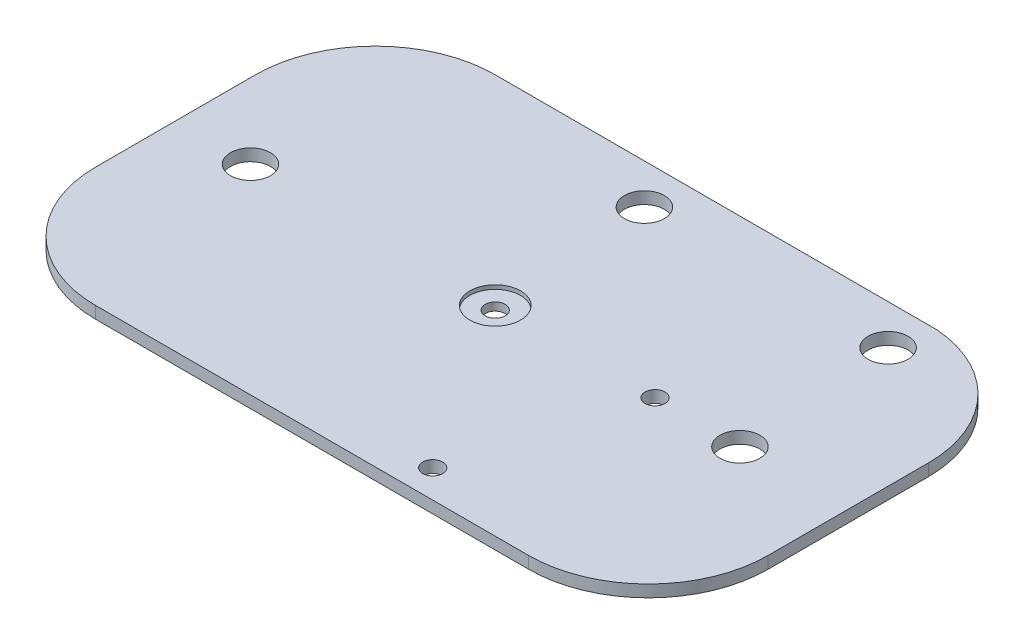
SolidWorks part; units mm, degrees
ref_plane "前视基准面" through (0, 0, 0) normal (0, 0, 1) x (1, 0, 0)
ref_plane "上视基准面" through (0, 0, 0) normal (0, 1, 0) x (1, 0, 0)
ref_plane "右视基准面" through (0, 0, 0) normal (1, 0, 0) x (0, 0, -1)
other "Configuration Table"
sketch "草图1" plane through (0, 0, 0) normal (0, 1, 0) x (1, 0, 0)
  line L0 (50, 0) -> (50, 85.1816) construction
  line L1 (0, 0) -> (100, 0)
  line L2 (0, 0) -> (0, -100)
  line L3 (0, -100) -> (100, -100)
  line L4 (100, 0) -> (100, -100)
  line L5 (9.5, 75.0478) -> (9.5, 17.1128) construction
  line L6 (90.5, 75.0478) -> (90.5, 17.1128) construction
  line L7 (-7.6482, 80) -> (134.4168, 80) construction
  line L8 (0, 0) -> (9.5, 12.5)
  line L9 (100, 0) -> (90.5, 12.5)
  line L10 (90.5, 12.5) -> (90.5, 212.5)
  line L11 (90.5, 212.5) -> (9.5, 212.5)
  line L12 (9.5, 212.5) -> (9.5, 12.5)
  line L13 (90.5, 12.5) -> (90.5, 0)
  line L14 (9.5, 12.5) -> (9.5, 0)
  dimension "D1" = 100
  dimension "D2" = 100
  dimension "D3" = 81
  dimension "D4" = 80
  dimension "D5" = 200
extrude "凸台-拉伸1" add sketch "草图1" along normal blind 50 and the other way blind 50 contours L12 L14 L1 L13 L10 L11 region at (50, 0, -106.25)
ref_plane "基准面1" through (0, 0, 0) normal (0, -1, 0) x (-1, 0, 0)
sketch "草图2" plane through (0, 0, 0) normal (0, -1, 0) x (-1, 0, 0)
  line L0 (-130.3132, 0) -> (40.2206, 0) construction
  line L1 (-150, 0) -> (-150, -100)
  line L2 (-150, -100) -> (50, -100)
  line L3 (50, -100) -> (50, 0)
  line L4 (50, 0) -> (-150, 0)
  line L5 (-50, 212.5) -> (-50, 195.989) construction
  line L6 (-90.5, 212.5) -> (-9.5, 212.5) construction
  point P10 (-50, 212.5)
  dimension "D1" = 200
  dimension "D2" = 100
extrude "凸台-拉伸2" add sketch "草图2" against normal blind 40
ref_plane "基准面2" through (0, 0, 100) normal (0, 0, 1) x (1, 0, 0)
sketch "草图3" plane through (0, 0, 100) normal (0, 0, 1) x (1, 0, 0)
  line L0 (-50, 37) -> (150, 37)
  line L1 (-50, 40) -> (-50, 0) construction
  line L2 (150, 40) -> (150, 0) construction
  line L3 (150, 37) -> (150, 3)
  line L4 (150, 3) -> (-50, 3)
  line L5 (-50, 3) -> (-50, 37)
  line L6 (150, 0) -> (-50, 0) construction
  line L7 (150, 40) -> (-50, 40) construction
  dimension "D1" = 3
  dimension "D2" = 3
extrude "切除-拉伸1" cut sketch "草图3" against normal blind 100
ref_plane "基准面3" through (34.5, 0, 0) normal (-1, 0, 0) x (0, 0, 1)
ref_plane "基准面4" through (0, 50, 0) normal (0, 1, 0) x (1, 0, 0)
sketch "草图6" plane through (0, 50, 0) normal (0, 1, 0) x (1, 0, 0)
  line L0 (12.5, 212.5) -> (12.5, 5)
  line L1 (90.5, 212.5) -> (9.5, 212.5) construction
  line L2 (12.5, 5) -> (87.5, 5)
  line L3 (87.5, 5) -> (87.5, 212.5)
  line L4 (9.5, 212.5) -> (9.5, 0) construction
  line L5 (90.5, 212.5) -> (90.5, 0) construction
  line L7 (9.5, 0) -> (90.5, 0) construction
  dimension "D1" = 3
  dimension "D2" = 3
  dimension "D3" = 5
extrude "切除-拉伸2" cut sketch "草图6" against normal through all
ref_plane "基准面5" through (0, 40, 0) normal (0, 1, 0) x (1, 0, 0)
sketch "草图8" plane through (0, 40, 0) normal (0, 1, 0) x (1, 0, 0)
  line L0 (-50, -50) -> (102.2011, -50) construction
  line L1 (-50, -100) -> (-50, 0) construction
  line L2 (50, 0) -> (50, -100) construction
  line L3 (9.5, 0) -> (90.5, 0) construction
  line L4 (-22, -100) -> (22, -100) construction
  circle A0 centre (70, -50) radius 2.5
  circle A1 centre (30, -50) radius 2.5
  dimension "D1" = 5
  dimension "D2" = 5
  dimension "D3" = 40
extrude "切除-拉伸4" cut sketch "草图8" against normal through all
ref_plane "基准面6" through (90.5, 0, 0) normal (1, 0, 0) x (0, 0, -1)
sketch "草图10" plane through (90.5, 0, 0) normal (1, 0, 0) x (0, 0, -1)
  line L0 (39.5916, 0) -> (155.7144, 0) construction
  line L2 (0, 37) -> (0, 3) construction
  circle A0 centre (80, 0) radius 5
  circle A1 centre (180, 0) radius 5
  dimension "D3" = 10
  dimension "D4" = 10
  dimension "D1" = 80
  dimension "D2" = 180
extrude "切除-拉伸5" cut sketch "草图10" against normal through all
sketch "草图11" plane through (9.5, 0, 0) normal (-1, 0, 0) x (0, 0, 1)
  line L2 (-30.9056, 83.4152) -> (-74.0944, 50)
  line L3 (44.55, 50) -> (-44.55, 50) construction
  line L4 (-74.0944, 50) -> (0, 50)
  line L5 (0, 40) -> (0, 50) construction
  line L6 (0, 50) -> (0, 40)
  line L8 (-30.9056, 83.4152) -> (83.321, 40)
  line L9 (100, 40) -> (0, 40) construction
  line L10 (83.321, 40) -> (0, 40)
extrude "凸台-拉伸5" add sketch "草图11" against normal blind 10
sketch "草图13" plane through (90.5, 0, 0) normal (1, 0, 0) x (0, 0, -1)
  line L0 (0, 36.2107) -> (0, 62.8442) construction
  line L1 (44.55, 50) -> (-44.55, 50) construction
  line L2 (74.1158, 50) -> (0, 50)
  line L3 (74.1158, 50) -> (74.1158, 53)
  line L4 (74.1158, 53) -> (0, 53)
  line L5 (0, 50) -> (0, 53)
  dimension "D1" = 3
extrude "凸台-拉伸7" add sketch "草图13" against normal blind 81
ref_plane "基准面7" through (12.5, 0, 0) normal (1, 0, 0) x (0, 0, -1)
sketch "草图14" plane through (12.5, 0, 0) normal (1, 0, 0) x (0, 0, -1)
  line L0 (5, -46.5508) -> (5, 34.4221) construction
  line L2 (5, -50) -> (212.5, -50)
  line L3 (212.5, -50) -> (212.5, 50)
  line L4 (44.55, 50) -> (-44.55, 50) construction
  line L5 (212.5, -50) -> (212.5, 50) construction
  line L6 (212.5, 50) -> (5, 50)
  line L7 (5, 50) -> (5, -50)
extrude "凸台-拉伸8" add sketch "草图14" along normal blind 7
sketch "草图15" plane through (90.5, 0, 0) normal (1, 0, 0) x (0, 0, -1)
  line L0 (30.9056, 83.4152) -> (-82.9022, 40)
  line L1 (55, 40) -> (-55, 40) construction
  line L2 (-82.9022, 40) -> (0, 40)
  line L3 (0, 37) -> (0, 40) construction
  line L4 (0, 40) -> (0, 53)
  line L5 (0, 53) -> (70.217, 53)
  line L6 (70.217, 53) -> (30.9056, 83.4152)
extrude "凸台-拉伸9" add sketch "草图15" against normal blind 10
ref_plane "基准面8" through (0, 37, 0) normal (0, -1, 0) x (-1, 0, 0)
ref_plane "基准面9" through (0, 3, 0) normal (0, 1, 0) x (1, 0, 0)
sketch "草图17" plane through (0, 37, 0) normal (0, -1, 0) x (-1, 0, 0)
  circle A0 centre (-30, -50) radius 6.35
  dimension "D1" = 12.7
extrude "切除-拉伸6" cut sketch "草图17" against normal blind 1
sketch "草图18" plane through (0, 3, 0) normal (0, 1, 0) x (1, 0, 0)
  circle A0 centre (30, -50) radius 6.35
  dimension "D1" = 12.7
extrude "切除-拉伸7" cut sketch "草图18" against normal blind 1
sketch "草图20" plane through (0, 0, 0) normal (0, -1, 0) x (1, 0, 0)
  line L0 (7.57, 50) -> (34.6356, 50) construction
  line L1 (30, 52.5) -> (30, 68.4286) construction
  circle A1 centre (-31.25, 50) radius 5
  circle A2 centre (91.25, 50) radius 5
  dimension "D2" = 10
  dimension "D4" = 10
  dimension "D1" = 61.25
  dimension "D3" = 61.25
extrude "切除-拉伸8" cut sketch "草图20" against normal blind 3
cosmetic thread "装饰螺纹线1" parameters "D2"=11
cosmetic thread "装饰螺纹线2" parameters "D2"=11
sketch "草图21" plane through (0, 3, 0) normal (0, 1, 0) x (1, 0, 0)
  line L0 (118.3346, -100) -> (118.3346, 0)
  line L1 (-22, -100) -> (22, -100) construction
  line L2 (90.5, 0) -> (150, 0) construction
  line L3 (118.3346, 0) -> (150, 0)
  line L4 (150, 0) -> (150, -100)
  line L5 (150, 0) -> (150, -100) construction
  line L6 (150, -100) -> (118.3346, -100)
extrude "切除-拉伸9" cut sketch "草图21" along normal through all both and the other way through all
sketch "草图22" plane through (0, 0, 0) normal (0, -1, 0) x (1, 0, 0)
  line L0 (-38.0419, 14.9384) -> (110.8032, 14.9384) construction
  circle A0 centre (-28.835, 14.9384) radius 5
  circle A1 centre (99.9437, 14.9384) radius 5
  circle A2 centre (47.3586, 88.9028) radius 5
  dimension "D1" = 10
  dimension "D2" = 10
  dimension "D3" = 10
extrude "凸台-拉伸10" add sketch "草图22" against normal up to surface (37 mm away) up to face at (70, 37, 52.5)
fillet "圆角1" radius 30 10 edges at (14.5, 83.4152, -30.9056) (85.5, 83.4152, -30.9056) (118.3346, 38.5, 0) (118.3346, 1.5, 0) (118.3346, 38.5, 100) (118.3346, 1.5, 100) (-50, 38.5, 100) (-50, 38.5, 0) (-50, 1.5, 0) (-50, 1.5, 100)
fillet "圆角2" radius 30 2 edges at (89, -50, -212.5) (89, 50, -212.5)
sketch "草图23" plane through (19.5, 0, 0) normal (1, 0, 0) x (0, 0, -1)
  line L0 (-82.9022, 40) -> (15.1729, 77.4135)
  line L1 (55, 40) -> (-55, 40) construction
  line L2 (15.1729, 77.4135) -> (-82.9022, 40) construction
  line L3 (15.1729, 77.4135) -> (30.2606, 83.1692)
  line L4 (30.2606, 83.1692) -> (82.9117, 53.4848)
  line L5 (82.9117, 53.4848) -> (216.9824, 51.4008)
  line L6 (216.9824, 51.4008) -> (216.9824, -53.0307)
  line L7 (216.9824, -53.0307) -> (0, -55.3463)
  line L8 (0, -55.3463) -> (0, 40)
  line L9 (0, 40) -> (-82.9022, 40)
  arc A0 (44.2235, 73.1112) -> (15.1729, 77.4135) centre (25.8656, 49.3838) ccw construction
extrude "切除-拉伸10" cut sketch "草图23" against normal through all both and the other way through all
ref_plane "基准面10" through (0, 0, 0) normal (0, -1, 0) x (-1, 0, 0)
sketch "草图24" plane through (0, 0, 0) normal (0, -1, 0) x (1, 0, 0)
  line L0 (-36.25, 50) -> (-26.25, 50) construction
  line L1 (-50, 66.8294) -> (-50, 70)
  line L2 (-50, 70) -> (-50, 30) construction
  line L3 (1.65, 100) -> (-1.65, 100) construction
  line L4 (-20, 100) -> (88.3346, 100)
  line L5 (118.3346, 70) -> (118.3346, 30)
  line L6 (88.3346, 0) -> (-20, 0)
  line L7 (-50, 0) -> (-50, 30)
  line L8 (-50, 30) -> (-50, 66.8294)
  line L9 (-20, 0) -> (90.5, 0) construction
  line L10 (118.3346, 29.9218) -> (118.3346, 70) construction
  circle A0 centre (-31.25, 50) radius 5 construction
  circle A1 centre (-31.25, 50) radius 5
  circle A2 centre (30, 50) radius 2.5
  circle A3 centre (70, 50) radius 2.5
  circle A4 centre (91.25, 50) radius 5
  arc A6 (118.3346, 70) -> (88.3346, 100) centre (88.3346, 70) ccw
  arc A7 (-50, 70) -> (-20, 100) centre (-20, 70) cw
  arc A8 (88.3346, 0) -> (118.3346, 30) centre (88.3346, 30) ccw
  arc A9 (-20, 0) -> (-50, 30) centre (-20, 30) cw
  point P35 (118.3346, 100)
  point P38 (-50, 100)
  dimension "D1" = 30
  dimension "D2" = 30
  dimension "D3" = 30
  dimension "D4" = 30
sketch "草图25" plane through (118.3346, 0, 0) normal (1, 0, 0) x (0, 0, -1)
  line L0 (-96.9992, 37) -> (-5.7141, 37)
  line L1 (-100, 37) -> (-70, 37) construction
  line L2 (-29.9218, 37) -> (0, 37) construction
  line L3 (-5.7141, 37) -> (-5.7141, 3)
  line L4 (55, 3) -> (-55, 3) construction
  line L5 (-5.7141, 3) -> (-98.6224, 3)
  line L6 (-98.6224, 3) -> (-96.9992, 37)
extrude "切除-拉伸11" cut sketch "草图25" against normal through all both and the other way through all
sketch "草图26" plane through (0, 0, 0) normal (0, -1, 0) x (1, 0, 0)
  line L1 (88.3346, 0) -> (88.3346, 38.8394) construction
  line L2 (27.3346, 31.1143) -> (27.3346, -2.0928) construction
  circle A1 centre (88.3346, 10) radius 5
  circle A2 centre (27.3346, 10) radius 5
  dimension "D1" = 10
  dimension "D4" = 10
  dimension "D2" = 10
  dimension "D3" = 61
extrude "切除-拉伸12" cut sketch "草图26" against normal through all both and the other way through all
sketch "草图27" plane through (34.5, 0, 0) normal (-1, 0, 0) x (0, 0, 1)
  line L0 (-18.9418, 81.6961) -> (-17.6639, 66.3073)
  line L1 (-17.6639, 66.3073) -> (80.7391, 40)
  line L2 (100, 40) -> (70, 40) construction
  line L3 (80.7391, 40) -> (87.3419, 40)
  line L4 (87.3419, 40) -> (-18.9418, 81.6961)
extrude "切除-拉伸13" cut sketch "草图27" against normal through all both and the other way through all
sketch "草图30" plane through (0, 37, 0) normal (0, -1, 0) x (1, 0, 0)
  circle A0 centre (88.3346, 10) radius 7.5
  dimension "D1" = 15
extrude "切除-拉伸14" cut sketch "草图30" against normal through all both and the other way through all
sketch "草图31" plane through (0, 37, 0) normal (0, -1, 0) x (1, 0, 0)
  circle A0 centre (27.3346, 10) radius 7.5
  dimension "D1" = 15
extrude "切除-拉伸15" cut sketch "草图31" against normal through all both and the other way through all
sketch "草图32" plane through (0, 0, 0) normal (0, -1, 0) x (1, 0, 0)
  circle A0 centre (27.3346, 10) radius 5
  circle A1 centre (27.3346, 10) radius 7.5
  dimension "D1" = 10
extrude "凸台-拉伸12" add sketch "草图32" against normal blind 3
sketch "草图33" plane through (0, 0, 0) normal (0, -1, 0) x (1, 0, 0)
  circle A0 centre (88.3346, 10) radius 5
  circle A1 centre (88.3346, 10) radius 7.5
  dimension "D1" = 10
  dimension "D2" = 15
extrude "凸台-拉伸13" add sketch "草图33" against normal blind 3
sketch "草图34" plane through (0, 37, 0) normal (0, -1, 0) x (1, 0, 0)
  line L0 (27.3346, 10) -> (27.3346, 28.3647) construction
  line L1 (87.8566, 10) -> (87.8566, 33.5037) construction
  line L2 (57.3566, 24.8807) -> (57.3566, 51.8819) construction
  circle A0 centre (57.3566, 86.5535) radius 5
  dimension "D2" = 10
  dimension "D1" = 30.5
extrude "凸台-拉伸14" add sketch "草图34" along normal blind 45
sketch "草图35" plane through (0, 0, 0) normal (0, -1, 0) x (1, 0, 0)
  line L0 (90.066, 10) -> (90.066, 27.6962) construction
  line L1 (59.566, 10.7555) -> (59.566, 36.2698) construction
  dimension "D1" = 30.5
sketch "草图36" plane through (0, -8, 0) normal (0, -1, 0) x (1, 0, 0)
  circle A0 centre (57.3566, 86.5535) radius 2.5
  dimension "D1" = 5
sketch "草图41" plane through (90.5, 0, 0) normal (1, 0, 0) x (0, 0, -1)
  line L0 (55, 3) -> (-55, 3) construction
  line L1 (-110.5696, 47.1879) -> (17.3858, 47.1879)
  line L2 (-110.5696, 47.1879) -> (-110.5696, 3)
  line L3 (-110.5696, 3) -> (17.3858, 3)
  line L4 (17.3858, 47.1879) -> (17.3858, 3)
extrude "切除-拉伸19" cut sketch "草图41" against normal through all both and the other way through all
sketch "草图42" plane through (90.5, 0, 0) normal (1, 0, 0) x (0, 0, -1)
  line L0 (199989.2445, 0) -> (-200036.2698, 0) construction
  line L1 (-102.6317, 0) -> (-41.9354, 0)
  line L2 (-102.6317, 0) -> (-102.6317, -16.6949)
  line L3 (-102.6317, -16.6949) -> (-41.9354, -16.6949)
  line L4 (-41.9354, 0) -> (-41.9354, -16.6949)
extrude "切除-拉伸20" cut sketch "草图42" against normal through all both and the other way through all
sketch "草图43" plane through (0, 0, 0) normal (0, -1, 0) x (1, 0, 0)
  line L0 (57.3566, 86.5535) -> (57.3566, 95.4512) construction
sketch "草图44" plane through (0, 0, 0) normal (0, -1, 0) x (1, 0, 0)
  line L0 (57.3566, -199913.4465) -> (57.3566, 200095.4512) construction
  line L1 (-20, 100) -> (88.3346, 100) construction
  circle A0 centre (57.3566, 93) radius 2.5
  dimension "D1" = 5
  dimension "D2" = 7
extrude "切除-拉伸21" cut sketch "草图44" against normal blind 10
sketch "草图45" plane through (0, 0, 0) normal (0, -1, 0) x (1, 0, 0)
  line L0 (-20, 0) -> (-20, 25.9767) construction
  line L1 (-20, 15) -> (69.4177, 15) construction
  line L2 (88.3346, 10) -> (88.3346, 24.4175) construction
  circle A0 centre (-20, 15) radius 5
  circle A1 centre (100.3346, 15) radius 5
  dimension "D1" = 10
  dimension "D3" = 10
  dimension "D2" = 15
  dimension "D4" = 12
